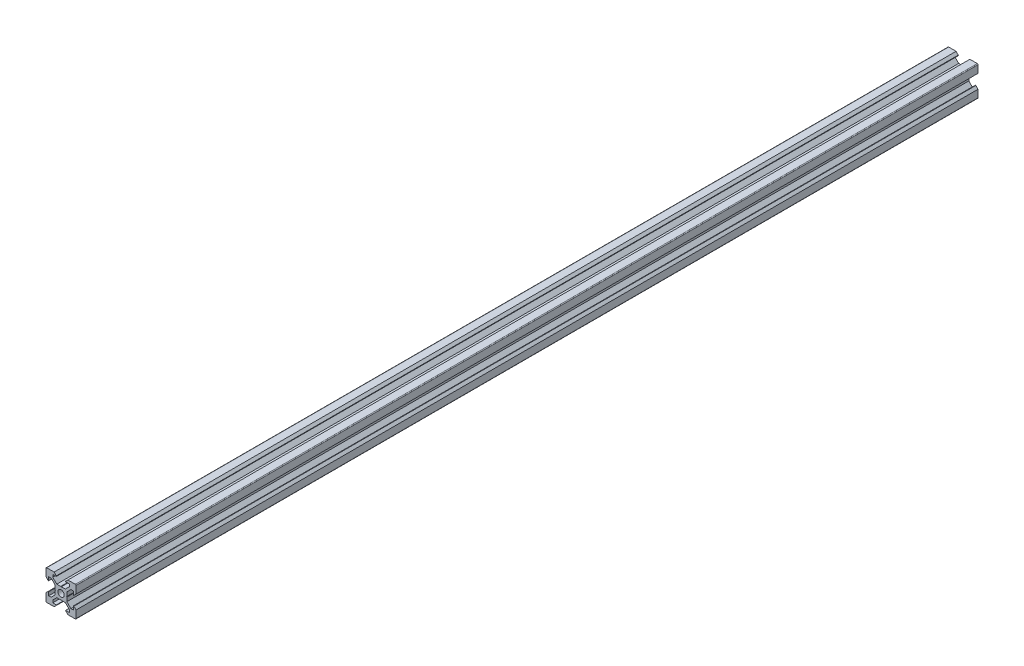
SolidWorks part; units mm, degrees
material "6061-T6 (SS)"
ref_plane "Front Plane" through (0, 0, 0) normal (0, 0, 1) x (1, 0, 0)
ref_plane "Top Plane" through (0, 0, 0) normal (0, 1, 0) x (1, 0, 0)
ref_plane "Right Plane" through (0, 0, 0) normal (1, 0, 0) x (0, 0, -1)
sketch "Sketch1" plane through (0, 0, 0) normal (0, 0, 1) x (1, 0, 0)
  line L1 (9.5, -10) -> (-9.5, -10)
  line L2 (10, -9.5) -> (10, 9.5)
  line L3 (9.5, 10) -> (-9.5, 10)
  line L4 (-10, -9.5) -> (-10, 9.5)
  line L5 (10, -10) -> (-10, 10) construction
  line L6 (10, 10) -> (-10, -10) construction
  circle A0 centre (0, 0) radius 2.1
  arc A1 (-9.5, 10) -> (-10, 9.5) centre (-9.5, 9.5) ccw
  arc A2 (10, 9.5) -> (9.5, 10) centre (9.5, 9.5) ccw
  arc A3 (9.5, -10) -> (10, -9.5) centre (9.5, -9.5) ccw
  arc A4 (-9.5, -10) -> (-10, -9.5) centre (-9.5, -9.5) cw
  point P0 (0, 0)
  line B0 (0, 0) -> (0, 10) construction
  line B1 (0, 3.69) -> (-0.21, 3.9)
  line B2 (-0.21, 3.9) -> (-2.8393, 3.9)
  line B3 (-2.8393, 3.9) -> (-5.5, 6.5607)
  line B4 (-5.5, 6.5607) -> (-5.5, 8.2)
  line B5 (-5.5, 8.2) -> (-3.125, 8.2)
  line B6 (-3.125, 8.2) -> (-3.125, 8.545)
  line B7 (-3.125, 8.545) -> (-4.58, 10)
  line B8 (-4.58, 10) -> (4.58, 10)
  line B9 (0, 0) -> (-5.9132, 5.9132) construction
  line B10 (3.125, 8.545) -> (4.58, 10)
  line B11 (3.125, 8.2) -> (3.125, 8.545)
  line B12 (5.5, 8.2) -> (3.125, 8.2)
  line B13 (5.5, 6.5607) -> (5.5, 8.2)
  line B14 (2.8393, 3.9) -> (5.5, 6.5607)
  line B15 (0.21, 3.9) -> (2.8393, 3.9)
  line B16 (0, 3.69) -> (0.21, 3.9)
  line B17 (0, 0) -> (-10, 0) construction
  line B18 (-3.69, 0) -> (-3.9, -0.21)
  line B19 (-3.9, -0.21) -> (-3.9, -2.8393)
  line B20 (-3.9, -2.8393) -> (-6.5607, -5.5)
  line B21 (-6.5607, -5.5) -> (-8.2, -5.5)
  line B22 (-8.2, -5.5) -> (-8.2, -3.125)
  line B23 (-8.2, -3.125) -> (-8.545, -3.125)
  line B24 (-8.545, -3.125) -> (-10, -4.58)
  line B25 (-10, -4.58) -> (-10, 4.58)
  line B26 (0, 0) -> (-5.9132, -5.9132) construction
  line B27 (-8.545, 3.125) -> (-10, 4.58)
  line B28 (-8.2, 3.125) -> (-8.545, 3.125)
  line B29 (-8.2, 5.5) -> (-8.2, 3.125)
  line B30 (-6.5607, 5.5) -> (-8.2, 5.5)
  line B31 (-3.9, 2.8393) -> (-6.5607, 5.5)
  line B32 (-3.9, 0.21) -> (-3.9, 2.8393)
  line B33 (-3.69, 0) -> (-3.9, 0.21)
  line B34 (0, 0) -> (0, -10) construction
  line B35 (0, -3.69) -> (0.21, -3.9)
  line B36 (0.21, -3.9) -> (2.8393, -3.9)
  line B37 (2.8393, -3.9) -> (5.5, -6.5607)
  line B38 (5.5, -6.5607) -> (5.5, -8.2)
  line B39 (5.5, -8.2) -> (3.125, -8.2)
  line B40 (3.125, -8.2) -> (3.125, -8.545)
  line B41 (3.125, -8.545) -> (4.58, -10)
  line B42 (4.58, -10) -> (-4.58, -10)
  line B43 (0, 0) -> (5.9132, -5.9132) construction
  line B44 (-3.125, -8.545) -> (-4.58, -10)
  line B45 (-3.125, -8.2) -> (-3.125, -8.545)
  line B46 (-5.5, -8.2) -> (-3.125, -8.2)
  line B47 (-5.5, -6.5607) -> (-5.5, -8.2)
  line B48 (-2.8393, -3.9) -> (-5.5, -6.5607)
  line B49 (-0.21, -3.9) -> (-2.8393, -3.9)
  line B50 (0, -3.69) -> (-0.21, -3.9)
  line B51 (0, 0) -> (10, 0) construction
  line B52 (3.69, 0) -> (3.9, 0.21)
  line B53 (3.9, 0.21) -> (3.9, 2.8393)
  line B54 (3.9, 2.8393) -> (6.5607, 5.5)
  line B55 (6.5607, 5.5) -> (8.2, 5.5)
  line B56 (8.2, 5.5) -> (8.2, 3.125)
  line B57 (8.2, 3.125) -> (8.545, 3.125)
  line B58 (8.545, 3.125) -> (10, 4.58)
  line B59 (10, 4.58) -> (10, -4.58)
  line B60 (0, 0) -> (5.9132, 5.9132) construction
  line B61 (8.545, -3.125) -> (10, -4.58)
  line B62 (8.2, -3.125) -> (8.545, -3.125)
  line B63 (8.2, -5.5) -> (8.2, -3.125)
  line B64 (6.5607, -5.5) -> (8.2, -5.5)
  line B65 (3.9, -2.8393) -> (6.5607, -5.5)
  line B66 (3.9, -0.21) -> (3.9, -2.8393)
  line B67 (3.69, 0) -> (3.9, -0.21)
  dimension "D1" = 4.2
  dimension "D3" = 0.5
  dimension "D2" = 20
sketch_block_instance "V Slot 1-4"
sketch_block "V Slot 1" parameters "D1"=10, "D2"=11, "D3"=4.3, "D4"=1.8, "D5"=0.21, "D6"=45, "D7"=9.16, "D8"=1.5, "D9"=6.25
sketch_block_instance "V Slot 1-5"
sketch_block_instance "V Slot 1-6"
sketch_block_instance "V Slot 1-7"
extrude "Boss-Extrude1" add sketch "Sketch1" along normal blind 600 contours B67 B52 B53 B54 B55 B56 B57 B58 L2 A2 L3 B10 B11 B12 B13 B14 B15 B16 B1 B2 B3 B4 B5 B6 B7 A1 L4 B27 B28 B29 B30 B31 B32 B33 B18 B19 B20 B21 B22 B23 B24 A4 L1 B44 B45 B46 B47 B48 B49 region at (7.04, -9.7172, 0)
